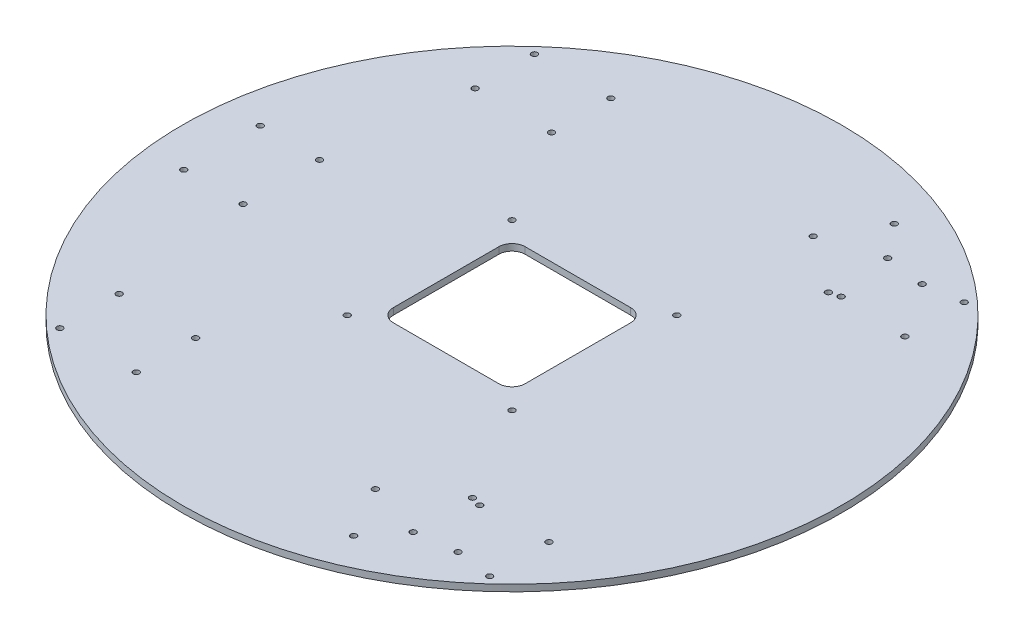
SolidWorks part; units mm, degrees
ref_plane "前视基准面" through (0, 0, 0) normal (0, 0, 1) x (1, 0, 0)
ref_plane "上视基准面" through (0, 0, 0) normal (0, 1, 0) x (1, 0, 0)
ref_plane "右视基准面" through (0, 0, 0) normal (1, 0, 0) x (0, 0, -1)
sketch "草图1" plane through (0, 0, 0) normal (0, 1, 0) x (1, 0, 0)
  circle A0 centre (0, 0) radius 250
  dimension "D1" = 500
extrude "凸台-拉伸1" add sketch "草图1" along normal blind 5
sketch "草图2" plane through (0, 5, 0) normal (0, 1, 0) x (1, 0, 0)
  line L0 (148.775, 179.6858) -> (116.275, 123.3942)
  line L1 (-230, -39) -> (-165, -39)
  line L2 (-230, -39) -> (-230, 39)
  line L3 (-230, 39) -> (-165, 39)
  line L4 (-165, -39) -> (-165, 39)
  line L5 (81.225, 218.6858) -> (148.775, 179.6858)
  line L6 (81.225, 218.6858) -> (48.725, 162.3942)
  line L7 (48.725, 162.3942) -> (116.275, 123.3942)
  line L8 (81.225, -218.6858) -> (48.725, -162.3942)
  line L9 (148.775, -179.6858) -> (81.225, -218.6858)
  line L10 (148.775, -179.6858) -> (116.275, -123.3942)
  line L11 (116.275, -123.3942) -> (48.725, -162.3942)
  circle A0 centre (-220, -29) radius 2.25
  circle A1 centre (-220, 29) radius 2.25
  circle A2 centre (-175, -29) radius 2.25
  circle A3 centre (-175, 29) radius 2.25
  circle A4 centre (84.8853, 205.0256) radius 2.25
  circle A5 centre (135.1147, 176.0256) radius 2.25
  circle A6 centre (62.3853, 166.0544) radius 2.25
  circle A7 centre (112.6147, 137.0544) radius 2.25
  circle A8 centre (135.1147, -176.0256) radius 2.25
  circle A9 centre (84.8853, -205.0256) radius 2.25
  circle A10 centre (112.6147, -137.0544) radius 2.25
  circle A11 centre (62.3853, -166.0544) radius 2.25
  point P40 (0, 0)
  dimension "D5" = 4.5
  dimension "D2" = 65
  dimension "D3" = 165
  dimension "D4" = 39
  dimension "D6" = 58
  dimension "D7" = 78
  dimension "D8" = 10
  dimension "D9" = 45
  dimension "D12" = 10
  dimension "D14" = 3
extrude "切除-拉伸1" cut sketch "草图2" against normal through all contours A4 | A5 | A6 | A7 | A1 | A0 | A3 | A2 | A11 | A10 | A9 | A8
sketch "草图3" plane through (0, 5, 0) normal (0, 1, 0) x (1, 0, 0)
  line L0 (0, 0) -> (0, 64.2236) construction
  line L1 (0, 0) -> (135.4837, 0) construction
  line L2 (95, 190) -> (95, 125)
  line L3 (173, 125) -> (95, 125)
  line L4 (173, 190) -> (173, 125)
  line L5 (-173, 190) -> (-95, 190)
  line L6 (-173, 190) -> (-173, 125)
  line L7 (-173, 125) -> (-95, 125)
  line L8 (-95, 190) -> (-95, 125)
  line L9 (173, 190) -> (95, 190)
  line L10 (173, -190) -> (95, -190)
  line L11 (-95, -190) -> (-95, -125)
  line L12 (-173, -125) -> (-95, -125)
  line L13 (-173, -190) -> (-173, -125)
  line L14 (-173, -190) -> (-95, -190)
  line L15 (173, -190) -> (173, -125)
  line L16 (173, -125) -> (95, -125)
  line L17 (95, -190) -> (95, -125)
  circle A0 centre (163, 135) radius 2.25
  circle A1 centre (105, 135) radius 2.25
  circle A2 centre (105, 180) radius 2.25
  circle A3 centre (163, 180) radius 2.25
  circle A4 centre (-163, 180) radius 2.25
  circle A5 centre (-105, 180) radius 2.25
  circle A6 centre (-105, 135) radius 2.25
  circle A7 centre (-163, 135) radius 2.25
  circle A8 centre (-163, -135) radius 2.25
  circle A9 centre (-105, -135) radius 2.25
  circle A10 centre (-105, -180) radius 2.25
  circle A11 centre (-163, -180) radius 2.25
  circle A12 centre (163, -180) radius 2.25
  circle A13 centre (105, -180) radius 2.25
  circle A14 centre (105, -135) radius 2.25
  circle A15 centre (163, -135) radius 2.25
  circle A16 centre (-62.5, 62.5) radius 2.25
  circle A17 centre (62.5, 62.5) radius 2.25
  circle A18 centre (62.5, -62.5) radius 2.25
  circle A19 centre (-62.5, -62.5) radius 2.25
  dimension "D2" = 4.5
  dimension "D10" = 4.5
  dimension "D3" = 62.5
  dimension "D4" = 62.5
  dimension "D8" = 65
  dimension "D9" = 78
  dimension "D11" = 45
  dimension "D12" = 58
  dimension "D13" = 10
  dimension "D14" = 10
  dimension "D15" = 125
  dimension "D16" = 95
extrude "切除-拉伸2" cut sketch "草图3" against normal through all contours A3 | A0 | A1 | A2 | A5 | A6 | A7 | A4 | A8 | A9 | A11 | A10 | A12 | A13 | A14 | A15 | A17 | A16 | A19 | A18
sketch "Sketch2" plane through (0, 0, 0) normal (0, -1, 0) x (1, 0, 0)
  line L1 (-50, 40) -> (-50, -40)
  line L2 (-40, -50) -> (40, -50)
  line L3 (50, -40) -> (50, 40)
  line L4 (40, 50) -> (-40, 50)
  arc A0 (50, 40) -> (40, 50) centre (40, 40) ccw
  circle A1 centre (0, 0) radius 50 construction
  arc A2 (40, -50) -> (50, -40) centre (40, -40) ccw
  arc A3 (-50, -40) -> (-40, -50) centre (-40, -40) ccw
  arc A4 (-50, 40) -> (-40, 50) centre (-40, 40) cw
  point P13 (-50, -50)
  point P16 (-50, 50)
  dimension "D1" = 10
  dimension "D2" = 100
extrude "Cut-Extrude4" cut sketch "Sketch2" against normal through all
